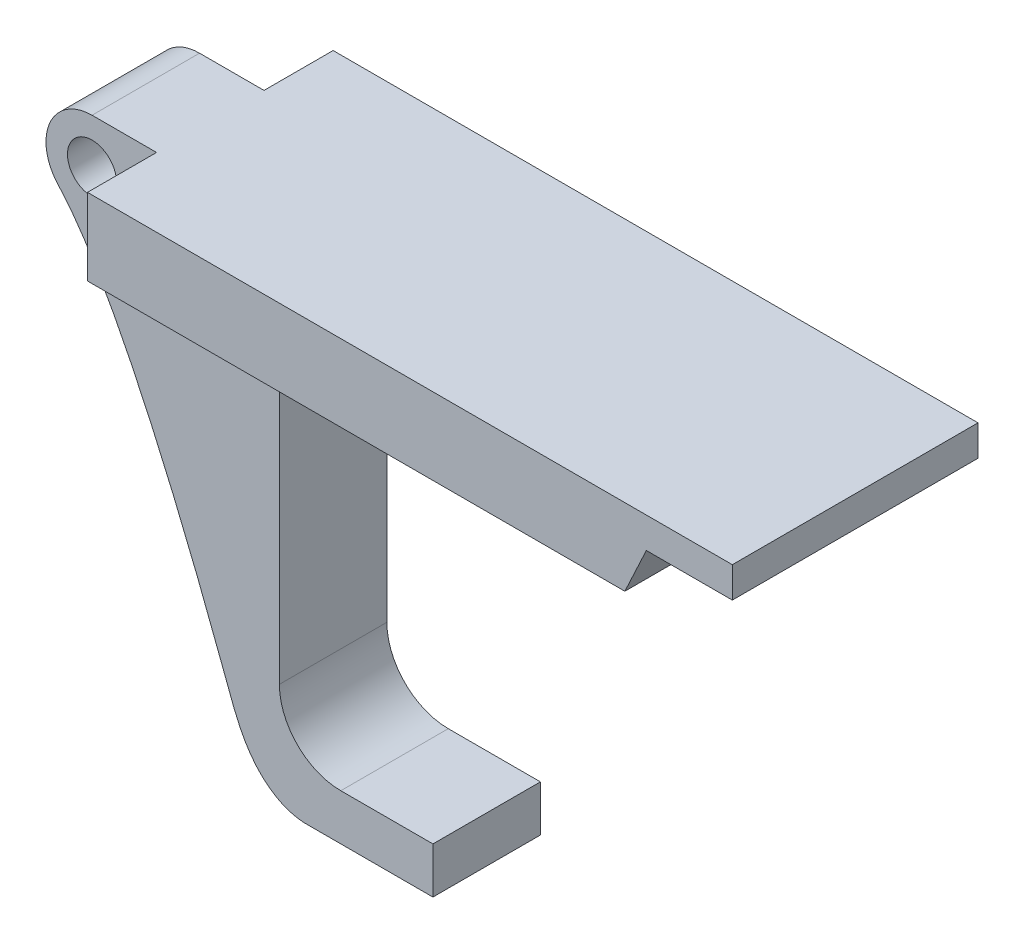
SolidWorks part; units mm, degrees
ref_plane "Ebene vorne" through (0, 0, 0) normal (0, 0, 1) x (1, 0, 0)
ref_plane "Ebene oben" through (0, 0, 0) normal (0, 1, 0) x (1, 0, 0)
ref_plane "Ebene rechts" through (0, 0, 0) normal (1, 0, 0) x (0, 0, -1)
sketch "Sketch1" plane through (0, 0, 0) normal (0, 1, 0) x (1, 0, 0)
  line L0 (-21, -8) -> (-21, -3.5)
  line L1 (-21, -8) -> (21, -8)
  line L2 (-21, 8) -> (21, 8)
  line L3 (21, -8) -> (21, 8)
  line L4 (-21, -8) -> (21, 8) construction
  line L5 (-21, 8) -> (21, -8) construction
  line L6 (-21, 3.5) -> (-21, 8)
  line L7 (-21, -3.5) -> (-28.2, -3.5)
  line L9 (-21, 3.5) -> (-28.2, 3.5)
  line L10 (-28.2, -3.5) -> (-28.2, 3.5)
  point P1 (0, 0)
  dimension "D1" = 16
  dimension "D2" = 42
  dimension "D3" = 7.2
  dimension "D4" = 7
extrude "Boss-Extrude1" add sketch "Sketch1" along normal blind 5
sketch "Sketch16" plane through (0, 0, 0) normal (0, -1, 0) x (1, 0, 0)
  line L1 (-21, 3.5) -> (-28.2, 3.5)
  line L2 (-21, 3.5) -> (-21, -3.5)
  line L3 (-21, -3.5) -> (-28.2, -3.5)
  line L4 (-28.2, 3.5) -> (-28.2, -3.5)
extrude "Boss-Extrude3" add sketch "Sketch16" along normal blind 1
sketch "Sketch17" plane through (0, 0, -3.5) normal (0, 0, -1) x (-1, 0, 0)
  line L0 (21, 5) -> (28.2, 5) construction
  line L1 (28.2, 5) -> (28.2, -1) construction
  circle A0 centre (25.2, 2) radius 1.6
  dimension "D1" = 3.2
  dimension "D2" = 3
  dimension "D3" = 3
extrude "Cut-Extrude4" cut sketch "Sketch17" against normal up to next
fillet "Fillet4" radius 3 2 edges at (-28.2, -1, 0) (-28.2, 5, 0)
sketch "Sketch18" plane through (0, 0, -3.5) normal (0, 0, -1) x (-1, 0, 0)
  line L1 (13, -21) -> (13, 0)
  line L2 (-21, 0) -> (21, 0) construction
  line L3 (13, 0) -> (21, 0)
  line L5 (3, -28) -> (10.9538, -28)
  line L6 (3, -28) -> (3, -25)
  line L7 (3, -25) -> (9, -25)
  line L8 (28.1067, 0.7165) -> (26.6767, -0.8135) construction
  line L11 (21, 0) -> (21, -1)
  line L12 (21, -1) -> (27.3917, -0.0485)
  arc A0 (9, -25) -> (13, -21) centre (9, -21) ccw
  arc A4 (25.2, -1) -> (28.2, 2) centre (25.2, 2) ccw construction
  spline S0 degree 3 poles (10.9538, -28) (12.5005, -28.089) (14.8521, -26.9194) (18.6756, -16.3651) (23.8252, -3.8644) (27.3917, -0.0485) knots 0 0 0 0 0.247683 0.347683 1 1 1 1
  point P8 (15.7011, -24.4089)
  point P12 (23.1686, -5.0879)
  point P15 (13, -25)
  point P16 (21.671, -9.0586)
  point P17 (25.2, -1)
  point P18 (0, 0)
  point P19 (26.0557, -1)
  point P20 (0, 0)
  point P22 (26.7655, -1)
  point P23 (0, 0)
  point P24 (0, 0)
  point P25 (26.483, -1)
  point P27 (26.7559, -0.565)
  point P34 (27.0242, -0.3817)
  point P37 (0, 0)
  dimension "D3" = 4
  dimension "D1" = 25
  dimension "D2" = 3
  dimension "D4" = 10
  dimension "D5" = 8
extrude "Boss-Extrude4" add sketch "Sketch18" against normal up to surface (7 mm away) up to face at (-26.8, 2, 3.5)
sketch "Sketch15" plane through (0, 0, 0) normal (0, -1, 0) x (1, 0, 0)
  line L0 (0, 0) -> (2, 0) construction
  line L1 (0, 3.5) -> (2, 3.5)
  line L2 (0, -3.5) -> (2, -3.5)
  line L7 (-3, 3.5) -> (-10.9538, 3.5)
  line L8 (-10.9538, 3.5) -> (-10.9538, -3.5)
  line L9 (-10.9538, -3.5) -> (-3, -3.5)
  line L10 (-3, -3.5) -> (-3, 3.5)
  line L11 (-3, 3.5) -> (-10.9538, 3.5) construction
  line L12 (-10.9538, 3.5) -> (-10.9538, -3.5) construction
  line L13 (-10.9538, -3.5) -> (-3, -3.5) construction
  line L14 (-3, -3.5) -> (-3, 3.5) construction
  arc A0 (0, 3.5) -> (0, -3.5) centre (0, 0) ccw
  arc A1 (2, -3.5) -> (2, 3.5) centre (2, 0) ccw
  point P3 (1, 0)
  dimension "D1" = 7
  dimension "D2" = 2
  dimension "D3" = 0
  dimension "D4" = 4
extrude "Cut-Extrude3" [suppressed] cut sketch "Sketch15" against normal up to next
fillet "Fillet5" radius 1 3 edges at (-17, 0, 3.5) (-13, 0, 0) (-17, 0, -3.5)
sketch "Sketch19" plane through (0, 0, 0) normal (0, -1, 0) x (1, 0, 0)
  line L0 (-21, 8) -> (21, 8) construction
  line L1 (14, 8) -> (21, 8)
  line L2 (14, 8) -> (14, -8)
  line L3 (14, -8) -> (21, -8)
  line L4 (21, 8) -> (21, -8)
  dimension "D1" = 7
extrude "Cut-Extrude5" cut sketch "Sketch19" against normal blind 3
chamfer "Chamfer1" distance 3 angle 25 1 edges at (14, 3, 0) first distance on face at (14, 1.5, 0)
